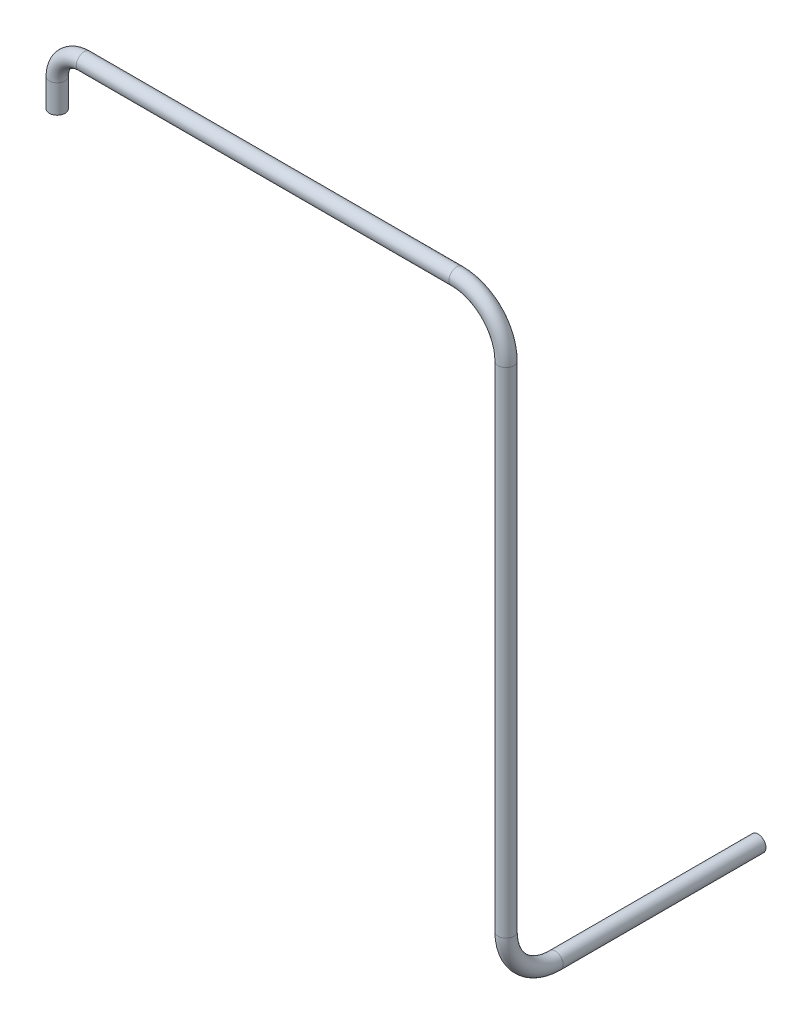
SolidWorks part; units mm, degrees
ref_plane "Front Plane" through (0, 0, 0) normal (0, 0, 1) x (1, 0, 0)
ref_plane "Top Plane" through (0, 0, 0) normal (0, 1, 0) x (1, 0, 0)
ref_plane "Right Plane" through (0, 0, 0) normal (1, 0, 0) x (0, 0, -1)
sketch "Sketch1" plane through (0, 0, 0) normal (0, 1, 0) x (1, 0, 0)
  circle A0 centre (0, 0) radius 4
  circle A1 centre (0, 0) radius 4
sketch3d "3DSketch1"
  line L0 (0, 0, 0) -> (0, 14.28, 0)
  line L1 (13.72, 28, 0) -> (203, 28, 0)
  line L2 (228, 3, 0) -> (228, -248, 0)
  line L3 (228, -273, -25) -> (228, -273, -128)
  arc A0 (0, 14.28, 0) -> (13.72, 28, 0) centre (13.72, 14.28, 0) cw
  arc A1 (203, 28, 0) -> (228, 3, 0) centre (203, 3, 0) cw
  arc A2 (228, -248, 0) -> (228, -273, -25) centre (228, -248, -25) cw
  point P4 (13.72, 14.28, -13.72)
  point P11 (203, 3, -25)
  point P18 (253, -248, -25)
sweep "Sweep1" add path "3DSketch1" circular profile diameter 8 parameters "D3"=8
sweep "Hollow_tube_OD_and_wall_PROVISIONAL" cut path "3DSketch1<2>" circular profile diameter 6 parameters "D3"=6
sketch3d "3DSketch1<2>" same geometry as "3DSketch1"
